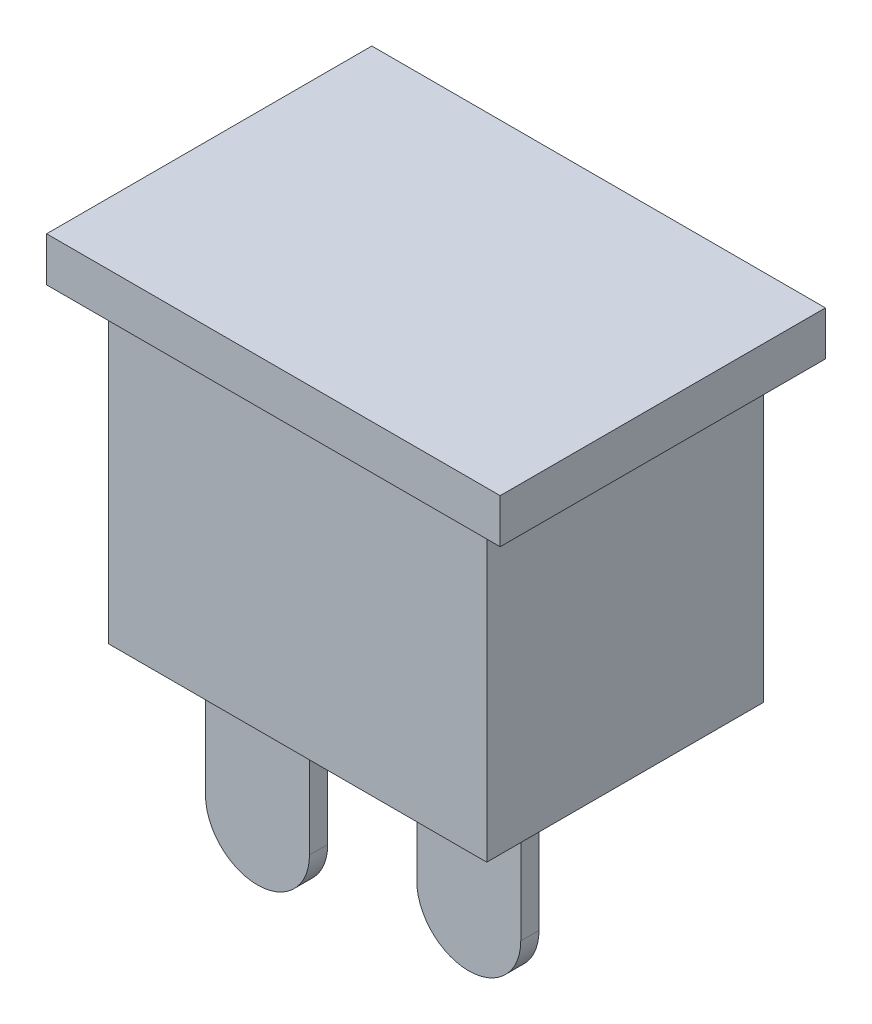
SolidWorks part; units mm, degrees
ref_plane "Front" through (0, 0, 0) normal (0, 0, 1) x (1, 0, 0)
ref_plane "Top" through (0, 0, 0) normal (0, 1, 0) x (1, 0, 0)
ref_plane "Right" through (0, 0, 0) normal (1, 0, 0) x (0, 0, -1)
sketch "Sketch1" plane through (0, 0, 0) normal (0, 1, 0) x (1, 0, 0)
  line L1 (0, 0) -> (17.3609, 0)
  line L2 (0, 0) -> (0, 12.7)
  line L3 (0, 12.7) -> (17.3609, 12.7)
  line L4 (17.3609, 0) -> (17.3609, 12.7)
  dimension "D1" = 17.3609
  dimension "D2" = 12.7
extrude "Boss-Extrude1" add sketch "Sketch1" against normal blind 13.97
sketch "Sketch2" plane through (0, 0, 0) normal (0, 1, 0) x (1, 0, 0)
  line L0 (0, 12.7) -> (0, 0) construction
  line L1 (-1.7336, -1.1176) -> (19.0944, -1.1176)
  line L2 (-1.7336, -1.1176) -> (-1.7336, 13.8176)
  line L3 (-1.7336, 13.8176) -> (19.0944, 13.8176)
  line L4 (19.0944, -1.1176) -> (19.0944, 13.8176)
  line L5 (17.3609, 12.7) -> (0, 12.7) construction
  point P6 (0, 6.35)
  point P7 (-1.7336, 6.35)
  point P10 (8.6804, 12.7)
  point P11 (8.6804, 13.8176)
  dimension "D1" = 20.828
  dimension "D2" = 14.9352
extrude "Boss-Extrude2" add sketch "Sketch2" along normal blind 2.032
sketch "Sketch3" plane through (0, -13.97, 0) normal (0, -1, 0) x (1, 0, 0)
  line L0 (0, -12.7) -> (0, 0) construction
  line L1 (2.54, -2.7432) -> (7.3152, -2.7432)
  line L2 (2.54, -2.7432) -> (2.54, -1.905)
  line L3 (2.54, -1.905) -> (7.3152, -1.905)
  line L4 (7.3152, -2.7432) -> (7.3152, -1.905)
  line L5 (10.8077, -4.1783) -> (15.5829, -4.1783)
  line L6 (10.8077, -4.1783) -> (10.8077, -3.3401)
  line L7 (10.8077, -3.3401) -> (15.5829, -3.3401)
  line L8 (15.5829, -4.1783) -> (15.5829, -3.3401)
  line L9 (17.3609, 0) -> (17.3609, -12.7) construction
  line L10 (0, 0) -> (17.3609, 0) construction
  line L11 (0, 0) -> (17.3609, 0) construction
  dimension "D1" = 4.7752
  dimension "D2" = 0.8382
  dimension "D3" = 2.54
  dimension "D4" = 1.778
  dimension "D5" = 3.3401
  dimension "D6" = 1.905
extrude "Boss-Extrude3" add sketch "Sketch3" along normal blind 8.0772
fillet "Fillet1" 2 edges at (2.54, -22.0472, -2.3241) (7.3152, -22.0472, -2.3241) type full round first side face at (2.54, -18.0086, -2.3241) second side face at (7.3152, -18.0086, -2.3241) middle face at (4.9276, -22.0472, -2.3241)
fillet "Fillet2" 2 edges at (10.8077, -22.0472, -3.7592) (15.5829, -22.0472, -3.7592) type full round first side face at (10.8077, -18.0086, -3.7592) second side face at (15.5829, -18.0086, -3.7592) middle face at (13.1953, -22.0472, -3.7592)
